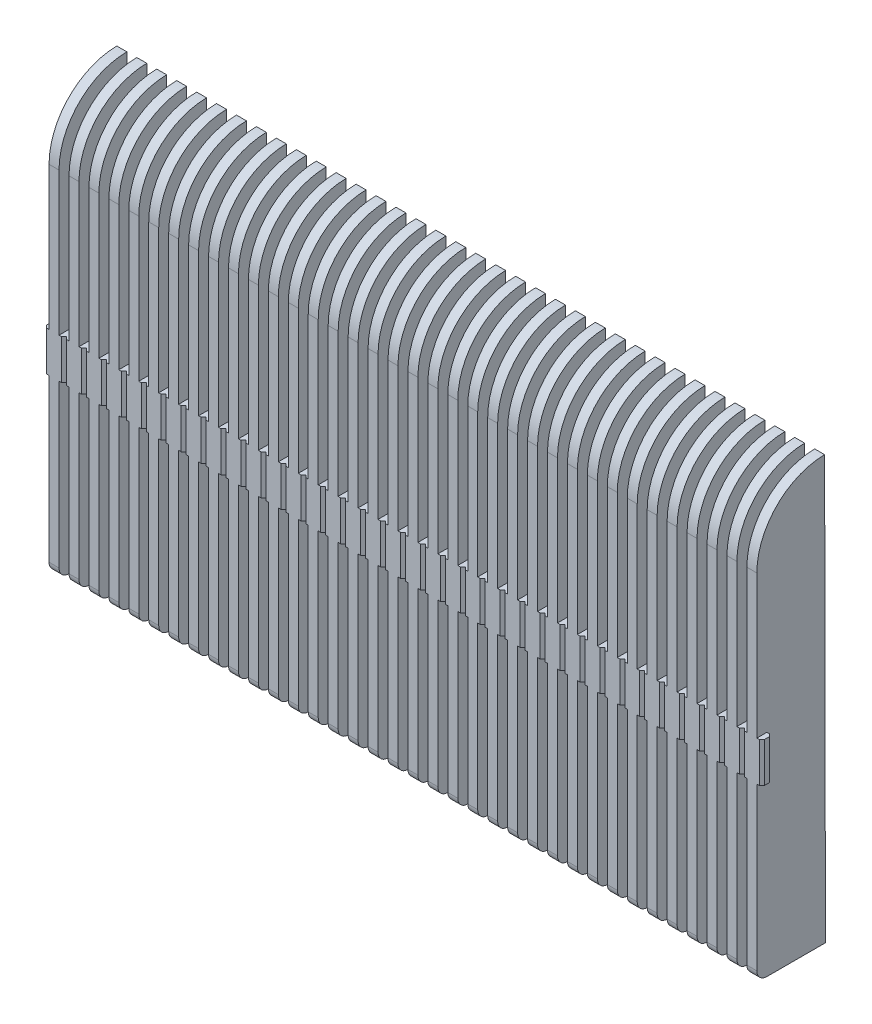
SolidWorks part; units mm, degrees
note: The reader was unsure of these and kept them because the rebuilt part matched: shared geometry of "Sketch6<5>".
ref_plane "Front Plane" through (0, 0, 0) normal (0, 0, 1) x (1, 0, 0)
ref_plane "Top Plane" through (0, 0, 0) normal (0, 1, 0) x (1, 0, 0)
ref_plane "Right Plane" through (0, 0, 0) normal (1, 0, 0) x (0, 0, -1)
sketch "Sketch1" plane through (0, 0, 0) normal (0, 1, 0) x (1, 0, 0)
  line L1 (-6.35, -17.272) -> (6.35, -17.272)
  line L2 (-6.35, -17.272) -> (-6.35, 17.272)
  line L3 (-6.35, 17.272) -> (6.35, 17.272)
  line L4 (6.35, -17.272) -> (6.35, 17.272)
  line L5 (-6.35, -17.272) -> (6.35, 17.272) construction
  line L6 (-6.35, 17.272) -> (6.35, -17.272) construction
  line L7 (-17.272, -6.35) -> (17.272, -6.35)
  line L8 (-17.272, -6.35) -> (-17.272, 6.35)
  line L9 (-17.272, 6.35) -> (17.272, 6.35)
  line L10 (17.272, -6.35) -> (17.272, 6.35)
  line L11 (-17.272, -6.35) -> (17.272, 6.35) construction
  line L12 (-17.272, 6.35) -> (17.272, -6.35) construction
  point P0 (0, 0)
  point P6 (0, 0)
  dimension "D1" = 12.7
  dimension "D2" = 34.544
  dimension "D3" = 34.544
  dimension "D4" = 12.7
extrude "Boss-Extrude1" add sketch "Sketch1" along normal blind 2.3813 contours L9 L8 L7 L2 | L9 L2 L7 L4 | L2 L9 L4 L3 | L7 L10 L9 L4 | L7 L2 L1 L4
sketch "Sketch2" plane through (0, 2.3813, 0) normal (0, 1, 0) x (1, 0, 0)
  line L1 (-6.35, -6.35) -> (6.35, -6.35)
  line L2 (-6.35, -6.35) -> (-6.35, 6.35)
  line L3 (-6.35, 6.35) -> (6.35, 6.35)
  line L4 (6.35, -6.35) -> (6.35, 6.35)
  line L5 (-6.35, -6.35) -> (6.35, 6.35) construction
  line L6 (-6.35, 6.35) -> (6.35, -6.35) construction
  point P0 (0, 0)
extrude "Boss-Extrude2" add sketch "Sketch2" along normal blind 67.3862
sketch "Sketch3" plane through (0, 69.7674, 0) normal (0, 1, 0) x (1, 0, 0)
  line L1 (-17.145, -17.145) -> (17.145, -17.145)
  line L2 (-17.145, -17.145) -> (-17.145, 17.145)
  line L3 (-17.145, 17.145) -> (17.145, 17.145)
  line L4 (17.145, -17.145) -> (17.145, 17.145)
  line L5 (-17.145, -17.145) -> (17.145, 17.145) construction
  line L6 (-17.145, 17.145) -> (17.145, -17.145) construction
  point P0 (0, 0)
  dimension "D1" = 34.29
  dimension "D2" = 34.29
extrude "Boss-Extrude3" add sketch "Sketch3" along normal blind 2.3813
fillet "Fillet15" radius 10.922 4 edges at (0, 69.7674, -6.35) (6.35, 69.7674, 0) (-6.35, 69.7674, 0) (0, 69.7674, 6.35)
sketch "Sketch4" plane through (0, 0, 0) normal (0, -1, 0) x (1, 0, 0)
  circle A0 centre (0, 0) radius 5.5562
  dimension "D1" = 11.1125
extrude "Cut-Extrude1" cut sketch "Sketch4" against normal blind 66.675 contours A0
sketch "Sketch5" plane through (0, 0, 0) normal (0, -1, 0) x (1, 0, 0)
  line L1 (-6.35, 6.35) -> (-3.175, 6.35)
  line L2 (-6.35, 6.35) -> (-6.35, 18.6009)
  line L3 (-6.35, 18.6009) -> (-3.175, 18.6009)
  line L4 (-3.175, 6.35) -> (-3.175, 18.6009)
  line L5 (6.35, 6.35) -> (3.175, 6.35)
  line L6 (6.35, 6.35) -> (6.35, 19.4213)
  line L7 (6.35, 19.4213) -> (3.175, 19.4213)
  line L8 (3.175, 6.35) -> (3.175, 19.4213)
  line L9 (6.35, 6.35) -> (22.2536, 6.35)
  line L10 (6.35, 6.35) -> (6.35, 3.175)
  line L11 (6.35, 3.175) -> (22.2536, 3.175)
  line L12 (22.2536, 6.35) -> (22.2536, 3.175)
  line L13 (6.35, -6.35) -> (23.7102, -6.35)
  line L14 (6.35, -6.35) -> (6.35, -3.175)
  line L15 (6.35, -3.175) -> (23.7102, -3.175)
  line L16 (23.7102, -6.35) -> (23.7102, -3.175)
  line L17 (6.35, -6.35) -> (3.175, -6.35)
  line L18 (6.35, -6.35) -> (6.35, -24.8431)
  line L19 (6.35, -24.8431) -> (3.175, -24.8431)
  line L20 (3.175, -6.35) -> (3.175, -24.8431)
  line L21 (-6.35, -6.35) -> (-3.175, -6.35)
  line L22 (-6.35, -6.35) -> (-6.35, -25.976)
  line L23 (-6.35, -25.976) -> (-3.175, -25.976)
  line L24 (-3.175, -6.35) -> (-3.175, -25.976)
  line L25 (-6.35, -6.35) -> (-27.5136, -6.35)
  line L26 (-6.35, -6.35) -> (-6.35, -3.175)
  line L27 (-6.35, -3.175) -> (-27.5136, -3.175)
  line L28 (-27.5136, -6.35) -> (-27.5136, -3.175)
  line L29 (-6.35, 6.35) -> (-27.5136, 6.35)
  line L30 (-6.35, 6.35) -> (-6.35, 3.175)
  line L31 (-6.35, 3.175) -> (-27.5136, 3.175)
  line L32 (-27.5136, 6.35) -> (-27.5136, 3.175)
  line M4 (17.272, 6.35) -> (6.35, 6.35)
  line M5 (6.35, 6.35) -> (6.35, 17.272)
  line M8 (-6.35, 17.272) -> (-6.35, 6.35)
  line M9 (-6.35, 6.35) -> (-17.272, 6.35)
  line M12 (-17.272, -6.35) -> (-6.35, -6.35)
  line M13 (-6.35, -6.35) -> (-6.35, -17.272)
  line M16 (6.35, -17.272) -> (6.35, -6.35)
  line M17 (6.35, -6.35) -> (17.272, -6.35)
  line M18 (-6.35, -17.272) -> (6.35, -17.272)
  line M19 (17.272, -6.35) -> (17.272, 6.35)
  line M20 (6.35, 17.272) -> (-6.35, 17.272)
  line M21 (-17.272, 6.35) -> (-17.272, -6.35)
  dimension "D1" = 3.175
  dimension "D2" = 3.175
  dimension "D3" = 3.175
  dimension "D4" = 3.175
  dimension "D5" = 3.175
  dimension "D6" = 3.175
  dimension "D7" = 3.175
  dimension "D8" = 3.175
extrude "Cut-Extrude2" cut sketch "Sketch5" against normal up to next contours L31 L30 M9 M21 | L1 L4 M20 M8 | L8 L5 M5 M20 | L10 L11 M19 M4 | L15 L14 M17 M19 | L17 L20 M18 M16 | L24 L21 M13 M18 | L26 L27 M21 M12
fillet "Fillet18" radius 3.175 8 edges at (-17.272, 1.1906, 3.175) (-17.272, 1.1906, -3.175) (-3.175, 1.1906, -17.272) (3.175, 1.1906, -17.272) (17.272, 1.1906, -3.175) (17.272, 1.1906, 3.175) (-3.175, 1.1906, 17.272) (3.175, 1.1906, 17.272)
fillet "Fillet28" radius 0.7937 8 edges at (6.35, 1.1906, 3.175) (3.175, 1.1906, 6.35) (6.35, 1.1906, -3.175) (3.175, 1.1906, -6.35) (-3.175, 1.1906, -6.35) (-6.35, 1.1906, -3.175) (-6.35, 1.1906, 3.175) (-3.175, 1.1906, 6.35)
fillet "Fillet29" radius 1.5875 4 edges at (-6.35, 2.3813, 0) (0, 2.3813, -6.35) (0, 2.3813, 6.35) (6.35, 2.3813, 0)
sketch "Sketch6" plane through (17.145, 0, 0) normal (1, 0, 0) x (0, 0, -1)
  line L0 (6.35, 58.8462) -> (6.35, 3.9688)
  line L1 (7.9375, 2.3812) -> (17.272, 2.3813)
  line L2 (17.272, 2.3813) -> (17.145, 69.7674)
  line L3 (17.145, 69.7674) -> (17.145, 72.1487)
  line L4 (17.145, 72.1487) -> (-17.145, 72.1487)
  line L5 (-17.145, 72.1487) -> (-17.145, 3.02)
  line L6 (-17.145, 3.02) -> (-18.4387, 3.02)
  line L7 (-18.4387, 3.02) -> (-18.4387, -0.492)
  line L8 (-18.4387, -0.492) -> (20.2416, -0.492)
  line L9 (20.2416, -0.492) -> (20.2416, 2.3813)
  line L10 (20.2416, 2.3813) -> (17.272, 2.3813)
  arc A0 (6.35, 58.8462) -> (17.145, 69.7674) centre (17.272, 58.8462) cw
  arc A1 (7.9375, 2.3812) -> (6.35, 3.9688) centre (7.9375, 3.9687) cw
  line M1 (-17.145, 69.7674) -> (17.145, 69.7674)
  line M2 (17.145, 69.7674) -> (17.145, 72.1487)
  line M3 (17.145, 72.1487) -> (-17.145, 72.1487)
  line M4 (-17.145, 72.1487) -> (-17.145, 69.7674)
extrude "Boss-Extrude4" add sketch "Sketch6" along normal blind 112.7125 separate body contours A1 L1 L2 A0 L0
extrude "Cut-Extrude4" cut sketch "Sketch6<5>" against normal mid plane 114.3 contours L1 A1 L0 A0 L5 L6 L7 L8 L9 L10 M1 | M4 M1 M2 M3
sketch "Sketch6<5>" plane through (17.145, 0, 0) normal (1, 0, 0) x (0, 0, -1) same geometry as "Sketch6"
sketch "Sketch7" plane through (0, 0, -6.35) normal (0, 0, 1) x (1, 0, 0)
  line L0 (129.8575, 69.7674) -> (17.145, 69.7674) construction
  line L1 (128.27, 69.7674) -> (126.6825, 69.7674)
  line L2 (128.27, 69.7674) -> (128.27, 2.3812)
  line L3 (128.27, 2.3812) -> (126.6825, 2.3812)
  line L4 (126.6825, 69.7674) -> (126.6825, 2.3812)
  line L5 (129.8575, 2.3812) -> (17.145, 2.3812) construction
  line L7 (129.8575, 58.8462) -> (129.8575, 3.9688) construction
  line L8 (17.9388, 69.7674) -> (17.9388, 2.3812)
  line L9 (17.145, 58.8462) -> (17.145, 3.9688) construction
  line L146 (17.9388, 69.7674) -> (17.145, 69.7674)
  line L147 (17.145, 69.7674) -> (17.145, 2.3812)
  line L148 (17.145, 2.3812) -> (17.9388, 2.3812)
  line L149 (17.9388, 2.3812) -> (17.7722, 2.2518)
  line L152 (129.8575, 69.7674) -> (134.9692, 69.7674)
  dimension "D1" = 1.5875
  dimension "D2" = 1.5875
  dimension "D3" = 0.7937
extrude "Cut-Extrude5" cut sketch "Sketch7" against normal blind 114.3 contours L2 L3 L4 L1
pattern_linear "LPattern1" count 35 spacing 3.175 along (-1, 0, 0) of "Cut-Extrude5"
sketch "Sketch8" plane through (129.8575, 0, 0) normal (1, 0, 0) x (0, 0, -1)
  line L1 (7.9375, 36.0743) -> (6.35, 36.0743)
  line L2 (7.9375, 36.0743) -> (7.9375, 29.7243)
  line L3 (7.9375, 29.7243) -> (6.35, 29.7243)
  line L4 (6.35, 36.0743) -> (6.35, 29.7243)
  line L5 (6.35, 58.8462) -> (6.35, 3.9688) construction
  dimension "D1" = 1.5875
  dimension "D2" = 6.35
  dimension "D3" = 0
extrude "Boss-Extrude5" add sketch "Sketch8" against normal blind 113.5063 and the other way blind 0.7937
sketch "Sketch9" plane through (0, 36.0743, 0) normal (0, 1, 0) x (1, 0, 0)
  line L0 (127.0794, 7.9375) -> (127.4763, 7.5406)
  line L1 (128.27, 7.9375) -> (126.6825, 7.9375) construction
  line L2 (127.4763, 7.5406) -> (127.8731, 7.9375)
  line L3 (127.8731, 7.9375) -> (127.0794, 7.9375)
  line L4 (126.6825, 7.1437) -> (128.27, 7.1437) construction
  line L5 (126.6825, 6.35) -> (126.6825, 7.9375) construction
  line L6 (128.27, 7.9375) -> (128.27, 6.35) construction
  line L7 (127.8731, 6.35) -> (127.0794, 6.35)
  line L8 (127.4763, 6.7469) -> (127.8731, 6.35)
  line L9 (127.0794, 6.35) -> (127.4763, 6.7469)
  dimension "D1" = 0.3969
  dimension "D2" = 0.3969
extrude "Cut-Extrude6" cut sketch "Sketch9" against normal through all
pattern_linear "LPattern2" count 36 spacing 3.175 along (-1, 0, 0) count 2 spacing 3.175 along (1, 0, 0) of "Cut-Extrude6"
